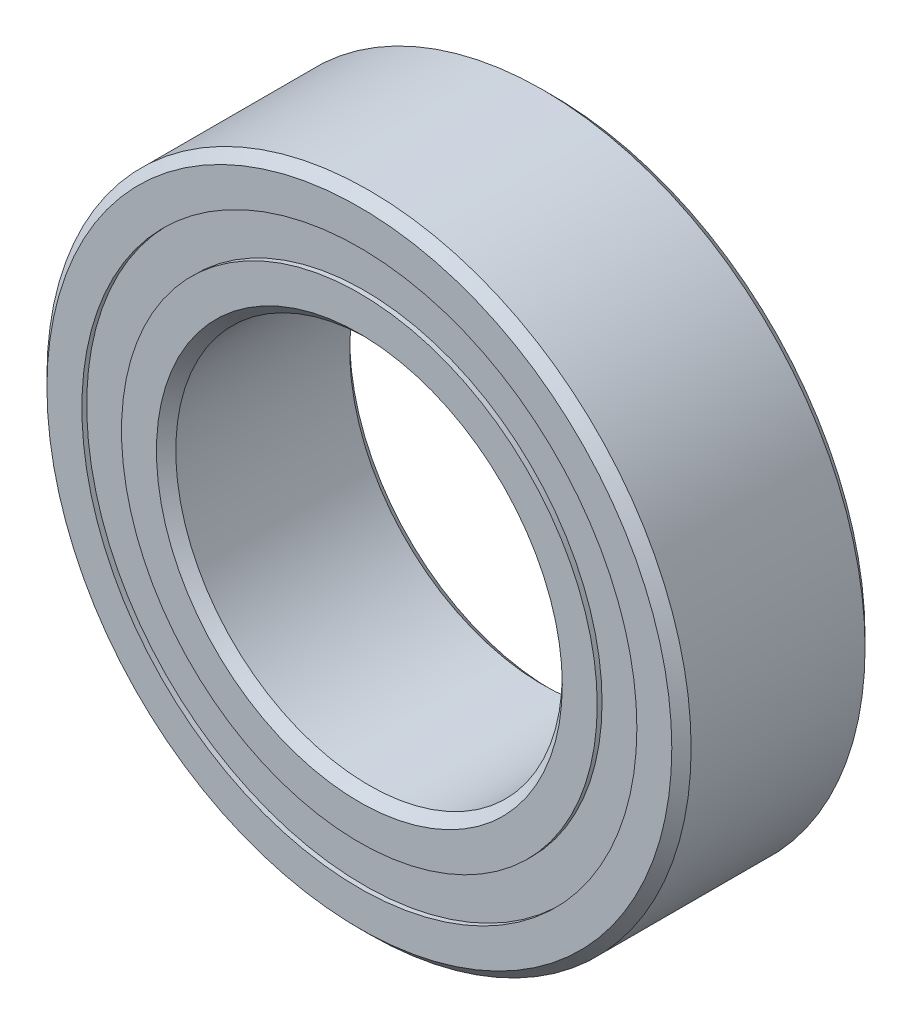
SolidWorks part; units mm, degrees
ref_plane "Front Plane" through (0, 0, 0) normal (0, 0, 1) x (1, 0, 0)
ref_plane "Top Plane" through (0, 0, 0) normal (0, 1, 0) x (1, 0, 0)
ref_plane "Right Plane" through (0, 0, 0) normal (1, 0, 0) x (0, 0, -1)
sketch "Sketch1" plane through (0, 0, 0) normal (1, 0, 0) x (0, 0, -1)
  line L0 (-1.5, 0) -> (1.5, 0) construction
  line L1 (0, 5) -> (0, -5) construction
  line L2 (1.35, 5) -> (-1.35, 5)
  line L3 (-1.35, 5) -> (-1.5, 4.85)
  line L4 (-1.5, 4.85) -> (-1.5, 4.3077)
  line L5 (-1.5, 4.3077) -> (-0.6667, 4.3077)
  line L6 (1.5, 4.3077) -> (0.6667, 4.3077)
  line L7 (1.5, 4.85) -> (1.5, 4.3077)
  line L8 (1.35, 5) -> (1.5, 4.85)
  line L9 (0, 5) -> (0, 4) construction
  line L10 (0, 4) -> (0, 3) construction
  arc A0 (-0.6667, 4.3077) -> (0.6667, 4.3077) centre (0, 4) cw
  point P14 (0, 3)
  dimension "Width" = 3
  dimension "OD" = 10
  dimension "D1" = 45
  dimension "D2" = 0.15
  dimension "Shaft Dia" = 6
  dimension "D3" = 1.3333
  dimension "D4" = 0.3077
revolve "Revolve1" add sketch "Sketch1" angle 360 about L0
sketch "Sketch3" plane through (0, 0, 0) normal (1, 0, 0) x (0, 0, -1)
  line L0 (-1.5, 3.6923) -> (-0.6667, 3.6923)
  line L1 (0, 5) -> (0, -5) construction
  line L2 (-1.5, 4.85) -> (-1.5, 4.3077) construction
  line L3 (-1.5, 3.6923) -> (-1.5, 3.15)
  line L4 (-1.35, 5) -> (-1.5, 4.85) construction
  line L5 (-1.5, 3.15) -> (-1.35, 3)
  line L6 (-1.35, 3) -> (1.35, 3)
  line L7 (1.35, 5) -> (1.35, -5) construction
  line L8 (1.35, 3) -> (1.5, 3.15)
  line L9 (1.5, -4.85) -> (1.5, 4.85) construction
  line L10 (1.5, 3.15) -> (1.5, 3.6923)
  line L11 (1.5, 3.6923) -> (0.6667, 3.6923)
  line L13 (1.35, 5) -> (1.5, 4.85) construction
  arc A0 (0.6667, 4.3077) -> (-0.6667, 4.3077) centre (0, 4) ccw construction
  arc A1 (0.6667, 3.6923) -> (-0.6667, 3.6923) centre (0, 4) cw
revolve "Revolve3" add sketch "Sketch3" angle 360 about L0
sketch "Sketch4" plane through (0, 0, 0) normal (1, 0, 0) x (0, 0, -1)
  line L0 (-0.7342, 4) -> (0.7342, 4)
  arc A2 (-0.7342, 4) -> (0.7342, 4) centre (0, 4) cw
  arc A3 (0.6667, 4.3077) -> (-0.6667, 4.3077) centre (0, 4) ccw construction
revolve "Revolve4" add sketch "Sketch4" angle 360 about L0
ref_axis "Axis1" through (0, 0, -1.5) along (0, 0, 1)
pattern_circular "CirPattern1" count 12 every 30 about axis through (0, 0, -1.5) along (0, 0, 1) of bodies 104
sketch "Sketch5" plane through (0, 0, 0) normal (1, 0, 0) x (0, 0, -1)
  line L0 (-1.5, 4.3077) -> (-0.6667, 4.3077) construction
  line L1 (-1.425, 4.3077) -> (-0.7342, 4.3077)
  line L2 (-1.425, 4.3077) -> (-1.425, 3.6923)
  line L3 (-1.425, 3.6923) -> (-0.7342, 3.6923)
  line L4 (-0.7342, 4.3077) -> (-0.7342, 3.6923)
  line L5 (-1.5, 3.6923) -> (-0.6667, 3.6923) construction
  line L6 (1.5, 4.3077) -> (0.6667, 4.3077) construction
  line L7 (1.425, 4.3077) -> (0.7342, 4.3077)
  line L8 (1.425, 4.3077) -> (1.425, 3.6923)
  line L9 (1.425, 3.6923) -> (0.7342, 3.6923)
  line L10 (0.7342, 4.3077) -> (0.7342, 3.6923)
  line L11 (1.5, 3.6923) -> (0.6667, 3.6923) construction
  line L12 (-1.35, 5) -> (-1.5, 4.85) construction
  point P18 (-1.425, 4.925)
revolve "Revolve5" add sketch "Sketch5" angle 360 about L0
sketch "Sketch6" plane through (0, 0, 0) normal (1, 0, 0) x (0, 0, -1)
  line L0 (1.5, 0) -> (-1.5, 0) construction
  line L1 (1.5, 4.3077) -> (0.4, 4.3077)
  line L2 (1.5, 4.3077) -> (1.5, 9.5)
  line L3 (1.5, 9.5) -> (0.4, 9.5)
  line L4 (0.4, 4.3077) -> (0.4, 9.5)
  dimension "Th" = 1.1
  dimension "Flange OD" = 19
revolve "Revolve6" [suppressed] add sketch "Sketch6" angle 360 about L0
equation "\"D2@Sketch1\" = \"Width@Sketch1\"*.05"
equation "\"D3@Sketch1\" = \"Width@Sketch1\"/2.25"
equation "\"D4@Sketch1\" = (((\"OD@Sketch1\"-\"Width@Sketch1\")/2)/3.25)/3.5"
equation "\"D2@CirPattern1\" = 360/\"Balls@CirPattern1\""
